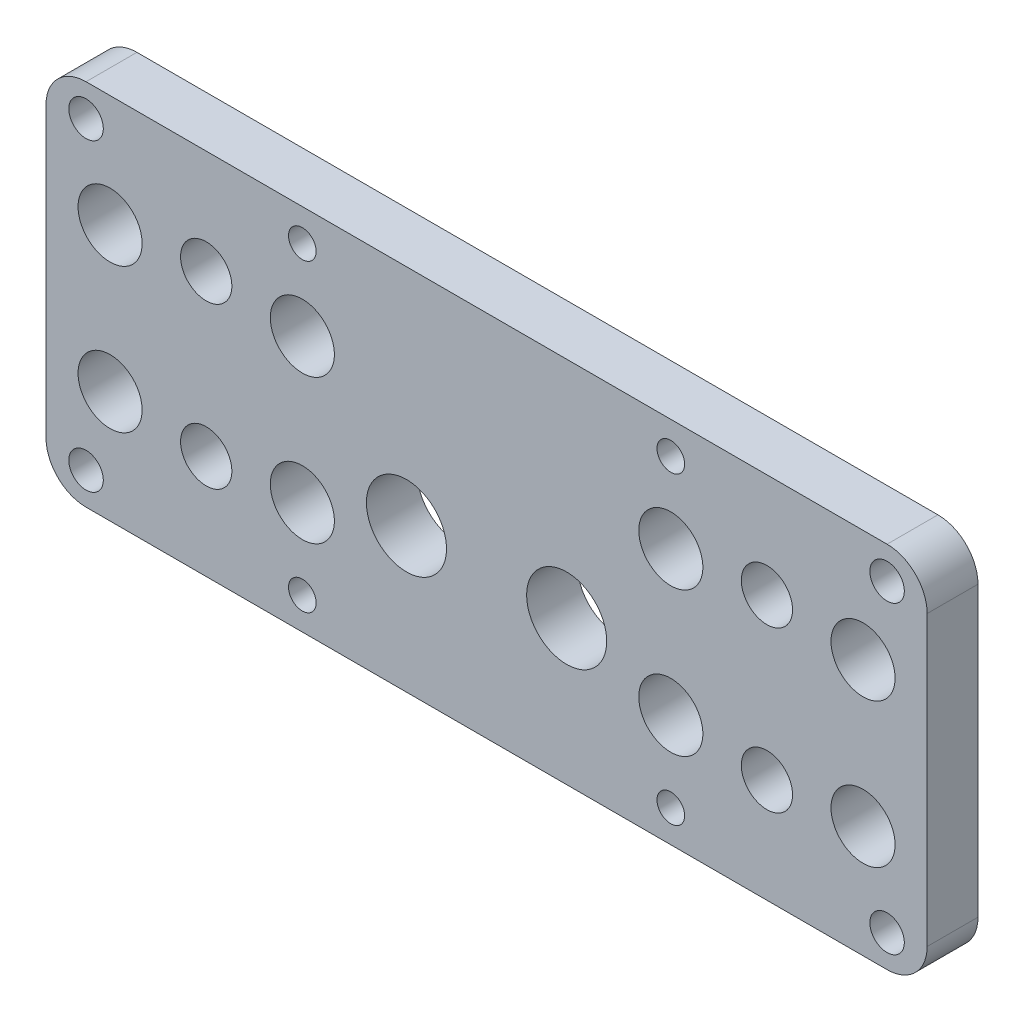
SolidWorks part; units mm, degrees
ref_plane "Front Plane" through (0, 0, 0) normal (0, 0, 1) x (1, 0, 0)
ref_plane "Top Plane" through (0, 0, 0) normal (0, 1, 0) x (1, 0, 0)
ref_plane "Right Plane" through (0, 0, 0) normal (1, 0, 0) x (0, 0, -1)
sketch "Sketch1" plane through (0, 0, 0) normal (0, 0, 1) x (1, 0, 0)
  line L0 (-55, -23) -> (-55, 23)
  line L1 (-55, -23) -> (55, -23)
  line L2 (-55, 23) -> (55, 23)
  line L3 (55, -23) -> (55, 23)
  line L4 (-55, -23) -> (55, 23) construction
  line L5 (-55, 23) -> (55, -23) construction
  point P1 (0, 0)
  dimension "D1" = 110
  dimension "D2" = 46
extrude "Boss-Extrude1" add sketch "Sketch1" along normal blind 6.35
sketch "Sketch2" plane through (0, 0, 0) normal (0, 0, -1) x (-1, 0, 0)
  line L0 (-35, -10) -> (-35, 10) construction
  line L1 (-35, -10) -> (35, -10) construction
  line L2 (-35, 10) -> (35, 10) construction
  line L3 (35, -10) -> (35, 10) construction
  line L4 (-35, -10) -> (35, 10) construction
  line L5 (-35, 10) -> (35, -10) construction
  point P1 (0, 0)
  dimension "D1" = 70
  dimension "D2" = 20
hole_wizard "M6 Clearance Hole1" positions "Sketch4" profile "Sketch3" hole size "M6" standard "ANSI Metric" end condition through all
sketch "Sketch4" plane through (0, 0, 0) normal (0, 0, -1) x (-1, 0, 0)
  point P0 (-35, 10)
  point P3 (-35, -10)
  point P6 (35, -10)
  point P9 (35, 10)
sketch "Sketch3" plane through (35, 10, 0) normal (1, 0, 0) x (0, 1, 0)
  line L0 (0, 0) -> (0, 6.35)
  line L1 (0, 6.35) -> (3.2, 6.35)
  line L2 (3.2, 6.35) -> (3.2, 0)
  line L5 (3.2, 0) -> (0, 0)
  line L11 (0, -6.35) -> (0, 107.95) construction
  dimension "Thru Hole Dia." = 6.4
  dimension "Thru Hole Depth" = 6.35
sketch "Sketch5" plane through (0, 0, 0) normal (0, 0, -1) x (-1, 0, 0)
  line L0 (-10, -5) -> (10, -5) construction
  circle A0 centre (-10, -5) radius 5
  circle A1 centre (10, -5) radius 5
  point P4 (0, -5)
  dimension "D2" = 10
  dimension "D3" = 10
  dimension "D1" = 20
  dimension "D4" = 5
extrude "Cut-Extrude1" cut sketch "Sketch5" against normal through all
sketch "Sketch7" plane through (0, 0, 0) normal (0, 0, -1) x (-1, 0, 0)
  line L1 (-23, -9) -> (23, -9) construction
  line L2 (-23, -9) -> (-23, 9) construction
  line L3 (-23, 9) -> (23, 9) construction
  line L4 (23, -9) -> (23, 9) construction
  line L5 (-23, -9) -> (23, 9) construction
  line L6 (-23, 9) -> (23, -9) construction
  line L7 (-47, -9) -> (-23, -9) construction
  line L8 (-47, -9) -> (-47, 9) construction
  line L9 (-47, 9) -> (-23, 9) construction
  line L10 (-23, -9) -> (-23, 9) construction
  line L11 (-47, -9) -> (-23, 9) construction
  line L12 (-47, 9) -> (-23, -9) construction
  line L13 (23, -9) -> (47, -9) construction
  line L14 (23, -9) -> (23, 9) construction
  line L15 (23, 9) -> (47, 9) construction
  line L16 (47, -9) -> (47, 9) construction
  line L17 (23, -9) -> (47, 9) construction
  line L18 (23, 9) -> (47, -9) construction
  circle A0 centre (-23, 9) radius 4
  circle A1 centre (-23, -9) radius 4
  circle A2 centre (23, -9) radius 4
  circle A3 centre (23, 9) radius 4
  circle A4 centre (-47, 9) radius 4
  circle A5 centre (-47, -9) radius 4
  circle A6 centre (47, 9) radius 4
  circle A7 centre (47, -9) radius 4
  point P0 (0, 0)
  point P10 (-35, 0)
  point P15 (35, 0)
  dimension "D3" = 8
  dimension "D1" = 46
  dimension "D2" = 18
  dimension "D4" = 24
  dimension "D5" = 24
extrude "Cut-Extrude2" cut sketch "Sketch7" against normal through all
sketch "Sketch8" plane through (0, 0, 0) normal (0, 0, -1) x (-1, 0, 0)
  line L1 (-23, -19) -> (23, -19) construction
  line L2 (-23, -19) -> (-23, 19) construction
  line L3 (-23, 19) -> (23, 19) construction
  line L4 (23, -19) -> (23, 19) construction
  line L5 (-23, -19) -> (23, 19) construction
  line L6 (-23, 19) -> (23, -19) construction
  line L7 (-50, -19) -> (50, -19) construction
  line L8 (-50, -19) -> (-50, 19) construction
  line L9 (-50, 19) -> (50, 19) construction
  line L10 (50, -19) -> (50, 19) construction
  line L11 (-50, -19) -> (50, 19) construction
  line L12 (-50, 19) -> (50, -19) construction
  point P0 (0, 0)
  point P6 (0, 0)
  dimension "D1" = 38
  dimension "D2" = 46
  dimension "D3" = 38
  dimension "D4" = 100
fillet "Fillet1" radius 5 4 edges at (-55, 23, 3.175) (-55, -23, 3.175) (55, -23, 3.175) (55, 23, 3.175)
hole_wizard "#8-32 Tapped Hole1" positions "Sketch10" profile "Sketch9" tap size "#8-32" standard "ANSI Inch" end condition through all
sketch "Sketch10" plane through (0, 0, 0) normal (0, 0, -1) x (-1, 0, 0)
  point P0 (-23, 19)
  point P3 (23, 19)
  point P6 (23, -19)
  point P9 (-23, -19)
sketch "Sketch9" plane through (23, 19, 0) normal (1, 0, 0) x (0, 1, 0)
  line L0 (0, 0) -> (0, 6.35)
  line L1 (0, 6.35) -> (1.7272, 6.35)
  line L2 (1.7272, 6.35) -> (1.7272, 0)
  line L5 (1.7272, 0) -> (0, 0)
  line L11 (0, -6.35) -> (0, 107.95) construction
  dimension "Thru Tap Drill Dia." = 3.4544
  dimension "Thru Tap Drill Depth" = 6.35
cosmetic thread "Hole Thread1" parameters "D2"=4.1656
cosmetic thread "Hole Thread2" parameters "D2"=4.1656
cosmetic thread "Hole Thread3" parameters "D2"=4.1656
cosmetic thread "Hole Thread4" parameters "D2"=4.1656
hole_wizard "#8 Clearance Hole1" positions "Sketch12" profile "Sketch11" hole size "#8" standard "ANSI Inch" end condition through all
sketch "Sketch12" plane through (0, 0, 0) normal (0, 0, -1) x (-1, 0, 0)
  point P0 (-50, 19)
  point P3 (-50, -19)
  point P6 (50, -19)
  point P9 (50, 19)
sketch "Sketch11" plane through (50, 19, 0) normal (1, 0, 0) x (0, 1, 0)
  line L0 (0, 0) -> (0, 6.35)
  line L1 (0, 6.35) -> (2.1526, 6.35)
  line L2 (2.1526, 6.35) -> (2.1526, 0)
  line L5 (2.1526, 0) -> (0, 0)
  line L11 (0, -6.35) -> (0, 107.95) construction
  dimension "Thru Hole Dia." = 4.3053
  dimension "Thru Hole Depth" = 6.35
